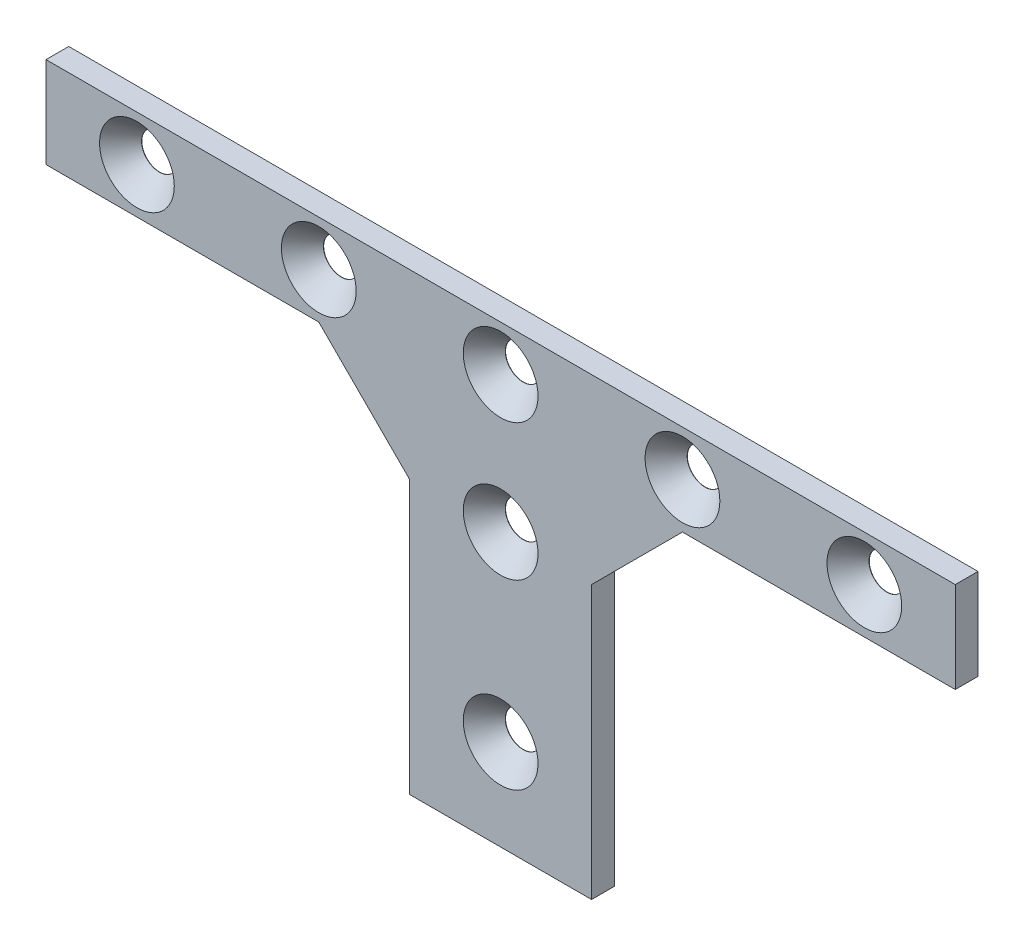
SolidWorks part; units mm, degrees
ref_plane "Front Plane" through (0, 0, 0) normal (0, 0, 1) x (1, 0, 0)
ref_plane "Top Plane" through (0, 0, 0) normal (0, 1, 0) x (1, 0, 0)
ref_plane "Right Plane" through (0, 0, 0) normal (1, 0, 0) x (0, 0, -1)
sketch "Sketch1" plane through (0, 0, 0) normal (0, 0, 1) x (1, 0, 0)
  line L0 (41.275, -25.4) -> (41.275, -63.5)
  line L2 (41.275, -63.5) -> (66.675, -63.5)
  line L4 (66.675, -63.5) -> (66.675, -25.4)
  line L5 (79.375, -12.7) -> (117.475, -12.7)
  line L7 (117.475, -12.7) -> (117.475, 0)
  line L9 (117.475, 0) -> (-9.525, 0)
  line L10 (-9.525, 0) -> (-9.525, -12.7)
  line L11 (-9.525, -12.7) -> (28.575, -12.7)
  line L13 (66.675, -25.4) -> (79.375, -12.7)
  line L14 (53.975, -12.7) -> (53.975, -25.4) construction
  line L15 (41.275, -25.4) -> (28.575, -12.7)
  line L16 (53.975, -63.5) -> (53.975, 0) construction
  line L17 (117.475, -6.35) -> (-9.525, -6.35) construction
  line L18 (117.475, -6.35) -> (104.775, -6.35) construction
  line L19 (104.775, -6.35) -> (79.375, -6.35) construction
  line L20 (79.375, -6.35) -> (53.975, -6.35) construction
  line L21 (53.975, -6.35) -> (28.575, -6.35) construction
  line L22 (28.575, -6.35) -> (3.175, -6.35) construction
  line L23 (53.975, -25.4) -> (53.975, -50.8) construction
  dimension "D1" = 19.05
  dimension "D2" = 25.4
  dimension "D3" = 127
extrude "Boss-Extrude1" add sketch "Sketch1" along normal blind 3.175
hole_wizard "#10 Clearance Hole1" positions "Sketch4" profile "Sketch5" hole size "#10" standard "ANSI Inch" end condition through all
sketch "Sketch4" plane through (0, 0, 3.175) normal (0, 0, 1) x (1, 0, 0)
  point P0 (3.175, -6.35)
  point P3 (28.575, -6.35)
  point P6 (53.975, -6.35)
  point P13 (104.775, -6.35)
  point P16 (53.975, -25.4)
  point P19 (53.975, -50.8)
  point P22 (79.375, -6.35)
sketch "Sketch5" plane through (3.175, -6.35, 3.175) normal (1, 0, 0) x (0, -1, 0)
  line L0 (0, 0) -> (0, 3.175)
  line L1 (0, 3.175) -> (2.4892, 3.175)
  line L2 (2.4892, 3.175) -> (2.4892, 3.1411)
  line L3 (2.4892, 3.1411) -> (5.2197, 0)
  line L5 (5.2197, 0) -> (0, 0)
  line L6 (-2.4892, 3.1411) -> (-5.2197, 0) construction
  line L11 (0, -6.35) -> (0, 107.95) construction
  dimension "Thru Hole Dia." = 4.9784
  dimension "Thru Hole Depth" = 3.175
  dimension "Near C'Sink Dia." = 10.4394
  dimension "Near C'Sink Angle" = 82
